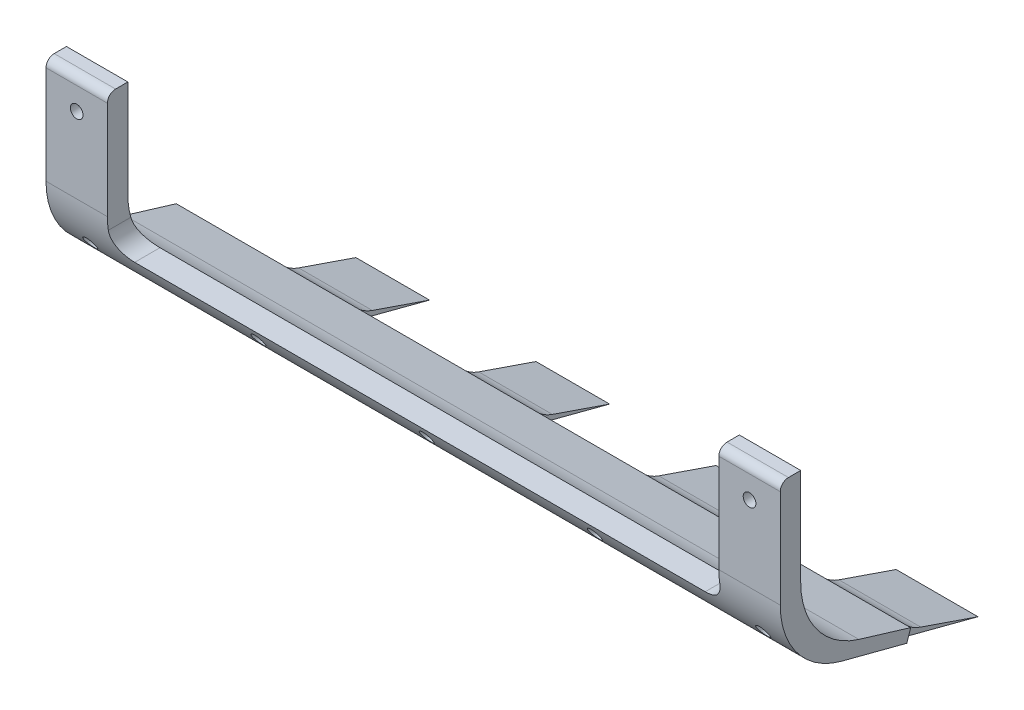
SolidWorks part; units mm, degrees
other "Markup1"
sketch "Sketch9" plane through (179.4, -40.9075, -59.0885) normal (0.9903, -0.01, -0.1384) x (-0.1383, 0.0097, -0.9903)
material "TPU"
ref_plane "Front Plane" through (0, 0, 0) normal (0, 0, 1) x (1, 0, 0)
ref_plane "Top Plane" through (0, 0, 0) normal (0, 1, 0) x (1, 0, 0)
ref_plane "Right Plane" through (0, 0, 0) normal (1, 0, 0) x (0, 0, -1)
sketch "Sketch1" plane through (0, 0, 0) normal (1, 0, 0) x (0, 0, -1)
  line L0 (0, 9.5114) -> (0, -30.4886) construction
  line L1 (0, -30.4886) -> (47.8152, -45.1072) construction
  line L2 (-2.5, 9.5114) -> (-2.5, -31.932)
  line L3 (2.5, 9.5114) -> (2.5, -29.0453)
  line L4 (-2.5, 9.5114) -> (2.5, 9.5114)
  line L9 (-2.5, 9.5114) -> (-2.5, -30.4886) construction
  line L10 (-2.5, -31.932) -> (47.8152, -45.1072)
  line L11 (2.5, 9.5114) -> (2.5, -30.4886) construction
  line L12 (29.3287, -37.1679) -> (28.4516, -40.0368) construction
  line L15 (47.8152, -45.1072) -> (28.8901, -38.6023)
  line L17 (28.8901, -38.6023) -> (29.3287, -37.1679)
  line L18 (29.3287, -37.1679) -> (2.5, -29.0453)
  point P15 (0, 0)
  point P17 (0, 0)
  dimension "D6" = 20
  dimension "D7" = 3
  dimension "D1" = 2.5
  dimension "D3" = 40
  dimension "D4" = 107
  dimension "D5" = 50
  dimension "D8" = 1.5
  dimension "D2" = 2.5
extrude "Boss-Extrude1" add sketch "Sketch1" along normal blind 179.4
fillet "Fillet3" radius 20 2 edges at (89.7, -31.932, 2.5) (89.7, -29.0453, -2.5)
sketch "Sketch3" plane through (0, 0, -2.5) normal (0, 0, -1) x (-1, 0, 0)
  line L0 (-179.4, 9.5114) -> (0, 9.5114) construction
  line L1 (-164.4, 9.5114) -> (-15, 9.5114)
  line L2 (-164.4, 9.5114) -> (-164.4, -24.4886)
  line L3 (-164.4, -24.4886) -> (-15, -24.4886)
  line L4 (-15, 9.5114) -> (-15, -24.4886)
  line L6 (-179.4, -14.2039) -> (-179.4, 9.5114) construction
  line L7 (0, -14.2039) -> (0, 9.5114) construction
  dimension "D1" = 34
  dimension "D2" = 15
  dimension "D3" = 15
extrude "Cut-Extrude2" cut sketch "Sketch3" against normal mid plane 180
fillet "Fillet5" radius 5 2 edges at (15, -24.4886, -2.257) (164.4, -24.4886, -2.257)
sketch "Sketch4" plane through (0, 0, -2.5) normal (0, 0, -1) x (-1, 0, 0)
  line L0 (-179.4, 9.5114) -> (-164.4, 9.5114) construction
  line L1 (-179.4, -14.2039) -> (-179.4, 9.5114) construction
  line L2 (-89.7, 9.5114) -> (-89.7, -73.3062) construction
  line L3 (-179.4, 9.5114) -> (0, 9.5114) construction
  circle A0 centre (-171.9, 2.0114) radius 1.55
  circle A1 centre (-7.5, 2.0114) radius 1.55
  dimension "D1" = 7.5
  dimension "D2" = 7.5
  dimension "D3" = 3.1
extrude "Cut-Extrude3" cut sketch "Sketch4" against normal up to next
sketch "Sketch6" plane through (0, 0, -2.5) normal (0, 0, -1) x (-1, 0, 0)
  line L0 (-171.9, 9.5114) -> (-171.9, -32.3844) construction
  line L1 (-179.4, 9.5114) -> (-164.4, 9.5114) construction
  line L2 (-171.9, -27.4886) -> (12.0668, -27.4886) construction
  circle A0 centre (-171.9, -27.4886) radius 1.55
  circle A1 centre (-130.8, -27.4886) radius 1.55
  circle A2 centre (-89.7, -27.4886) radius 1.55
  circle A3 centre (-48.6, -27.4886) radius 1.55
  circle A4 centre (-7.5, -27.4886) radius 1.55
  dimension "D1" = 3.1
  dimension "D2" = 37
  dimension "D3" = 5
extrude "Cut-Extrude4" cut sketch "Sketch6" against normal mid plane 180
sketch "Sketch10" plane through (0, -25.6428, 8.8139) normal (0, 0.9457, -0.3251) x (1, 0, 0)
  line L0 (179.4, 59.8809) -> (0, 59.8809) construction
  line L1 (177.4, 59.8809) -> (179.4, 59.8809)
  line L2 (177.4, 59.8809) -> (177.4, 39.8809)
  line L3 (177.4, 39.8809) -> (179.4, 39.8809)
  line L4 (179.4, 59.8809) -> (179.4, 39.8809)
  line L5 (179.4, 59.8809) -> (179.4, 39.8691) construction
  line L6 (193.4729, 48.0668) -> (-11.9509, 48.0668) construction
  line L7 (131.4, 59.8809) -> (157.4, 59.8809)
  line L8 (131.4, 59.8809) -> (131.4, 39.8809)
  line L9 (131.4, 39.8809) -> (157.4, 39.8809)
  line L10 (157.4, 59.8809) -> (157.4, 39.8809)
  line L11 (87.4, 59.8809) -> (87.4, 39.8809)
  line L12 (87.4, 59.8809) -> (113.4, 59.8809)
  line L13 (113.4, 59.8809) -> (113.4, 39.8809)
  line L14 (87.4, 39.8809) -> (113.4, 39.8809)
  line L15 (43.4, 59.8809) -> (43.4, 39.8809)
  line L16 (43.4, 59.8809) -> (69.4, 59.8809)
  line L17 (69.4, 59.8809) -> (69.4, 39.8809)
  line L18 (43.4, 39.8809) -> (69.4, 39.8809)
  line L19 (-0.6, 59.8809) -> (-0.6, 39.8809)
  line L20 (-0.6, 59.8809) -> (25.4, 59.8809)
  line L21 (25.4, 59.8809) -> (25.4, 39.8809)
  line L22 (-0.6, 39.8809) -> (25.4, 39.8809)
  dimension "D1" = 20
  dimension "D2" = 2
  dimension "D3" = 20
  dimension "D4" = 22
  dimension "D5" = 26
  dimension "D6" = 4
extrude "Cut-Extrude5" cut sketch "Sketch10" against normal up to next
fillet "Fillet7" radius 2 2 edges at (7.5, 9.5114, 2.5) (171.9, 9.5114, 2.5)
fillet "Fillet8" radius 10 1 edges at (89.7, -38.6023, -28.8901)
